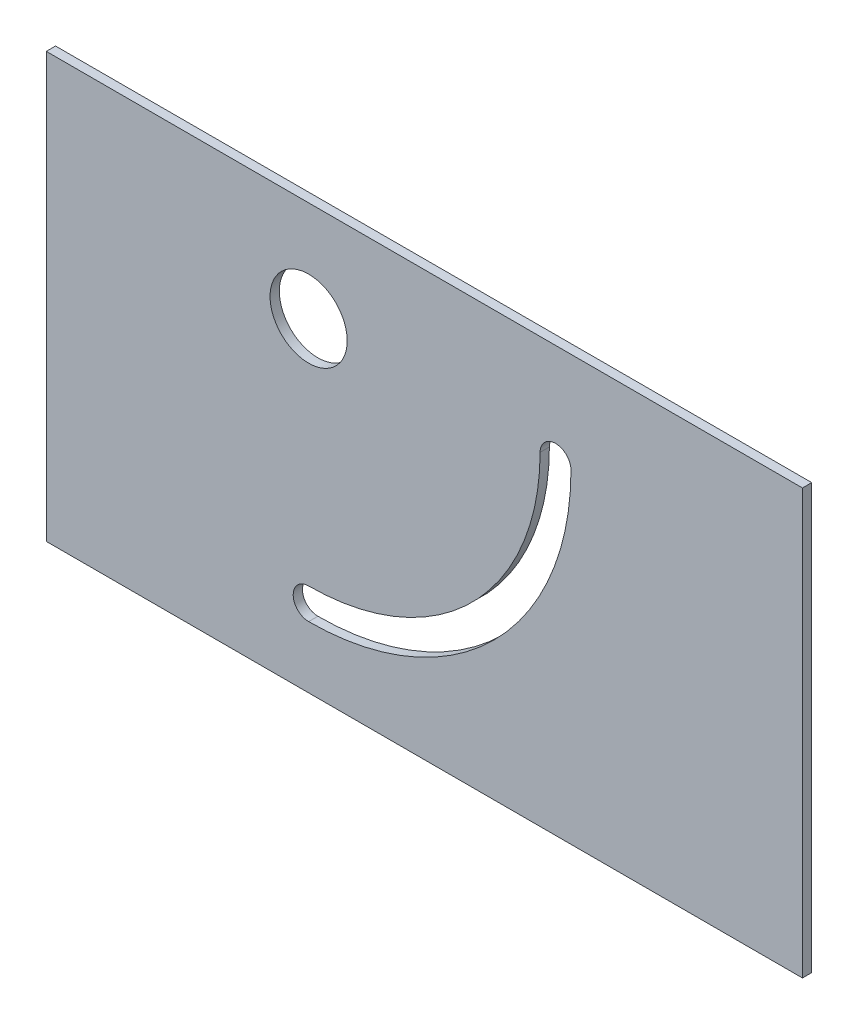
SolidWorks part; units mm, degrees
material "birch 3mm plywood"
ref_plane "Front Plane" through (0, 0, 0) normal (0, 0, 1) x (1, 0, 0)
ref_plane "Top Plane" through (0, 0, 0) normal (0, 1, 0) x (1, 0, 0)
ref_plane "Right Plane" through (0, 0, 0) normal (1, 0, 0) x (0, 0, -1)
sketch "Sketch1" plane through (0, 0, 0) normal (0, 0, 1) x (1, 0, 0)
  line L1 (-0.5, 137.5) -> (244.5, 137.5)
  line L2 (-0.5, 137.5) -> (-0.5, 0)
  line L3 (-0.5, 0) -> (244.5, 0)
  line L4 (244.5, 137.5) -> (244.5, 0)
  line L5 (84.5, 59.75) -> (84.5, -77.75) construction
  arc A3 (169.5, 105) -> (159.5, 105) centre (164.5, 105) ccw
  arc A4 (159.5, 105) -> (84.5, 30) centre (84.5, 105) cw
  arc A5 (169.5, 105) -> (84.5, 20) centre (84.5, 105) cw
  arc A6 (84.5, 20) -> (84.5, 30) centre (84.5, 25) cw
  circle A7 centre (84.5, 105) radius 12.5
  point P3 (0, 0)
  dimension "D1" = 10
  dimension "D2" = 75
  dimension "D3" = 20
  dimension "D7" = 25
  dimension "D4" = 20
  dimension "D5" = 85
  dimension "D6" = 160
extrude "Boss-Extrude1" add sketch "Sketch1" along normal blind 3
